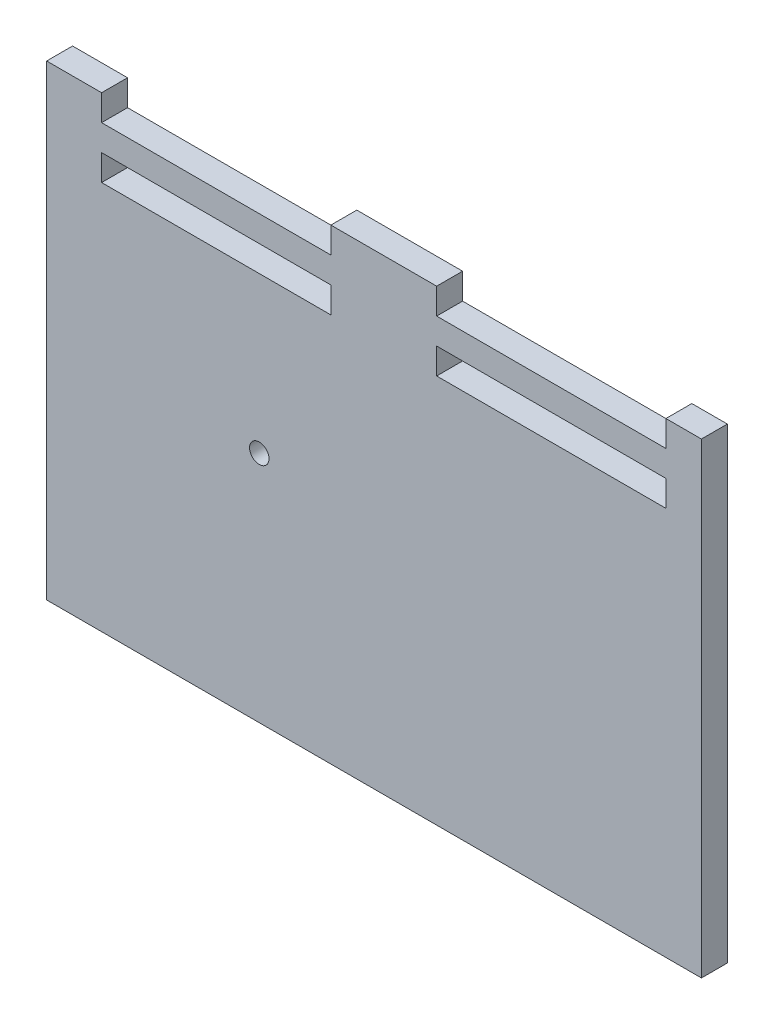
SolidWorks part; units mm, degrees
ref_plane "Front Plane" through (0, 0, 0) normal (0, 0, 1) x (1, 0, 0)
ref_plane "Top Plane" through (0, 0, 0) normal (0, 1, 0) x (1, 0, 0)
ref_plane "Right Plane" through (0, 0, 0) normal (1, 0, 0) x (0, 0, -1)
sketch "Sketch1" plane through (0, 0, 0) normal (0, 0, 1) x (1, 0, 0)
  line L1 (0, 0) -> (304.8, 0)
  line L2 (0, 0) -> (0, 228.6)
  line L3 (0, 228.6) -> (304.8, 228.6)
  line L4 (304.8, 0) -> (304.8, 228.6)
  dimension "D1" = 304.8
  dimension "D2" = 228.6
extrude "Boss-Extrude1" add sketch "Sketch1" along normal blind 12.7
sketch "Sketch2" plane through (0, 0, 12.7) normal (0, 0, 1) x (1, 0, 0)
  line L0 (304.8, 228.6) -> (0, 228.6) construction
  line L1 (0, 228.6) -> (0, 0) construction
  circle A0 centre (91.44, 114.3) radius 4.7625
  dimension "D1" = 9.525
  dimension "D2" = 114.3
  dimension "D3" = 91.44
extrude "Cut-Extrude1" cut sketch "Sketch2" against normal blind 12.7
sketch "Sketch6" plane through (0, 0, 12.7) normal (0, 0, 1) x (1, 0, 0)
  line L0 (0, 114.3) -> (304.8, 114.3) construction
  line L1 (0, 228.6) -> (0, 0) construction
  line L2 (304.8, 0) -> (304.8, 228.6) construction
sketch "Sketch7" plane through (0, 0, 12.7) normal (0, 0, 1) x (1, 0, 0)
  line L1 (14.224, 228.6) -> (126.492, 228.6)
  line L2 (14.224, 228.6) -> (14.224, 215.9)
  line L3 (14.224, 215.9) -> (126.492, 215.9)
  line L4 (0, 228.6) -> (0, 0)
  line L5 (0, 0) -> (304.8, 0)
  line L6 (304.8, 0) -> (304.8, 228.6)
  line L7 (304.8, 228.6) -> (0, 228.6)
  line L8 (0, 228.6) -> (0, 0)
  line L9 (0, 0) -> (304.8, 0)
  line L10 (304.8, 0) -> (304.8, 228.6)
  line L11 (304.8, 228.6) -> (0, 228.6)
  line L12 (126.492, 228.6) -> (126.492, 215.9)
  line L13 (178.308, 228.6) -> (290.576, 228.6)
  line L14 (178.308, 228.6) -> (178.308, 215.9)
  line L15 (178.308, 215.9) -> (290.576, 215.9)
  line L16 (290.576, 228.6) -> (290.576, 215.9)
  line L17 (14.224, 203.2) -> (126.492, 203.2)
  line L18 (14.224, 203.2) -> (14.224, 190.5)
  line L19 (14.224, 190.5) -> (126.492, 190.5)
  line L20 (126.492, 203.2) -> (126.492, 190.5)
  line L21 (178.308, 203.2) -> (290.576, 203.2)
  line L22 (178.308, 203.2) -> (178.308, 190.5)
  line L23 (178.308, 190.5) -> (290.576, 190.5)
  line L24 (290.576, 203.2) -> (290.576, 190.5)
  point P20 (70.358, 203.2)
  line M17 (304.8, 228.6) -> (0, 228.6)
  dimension "D2" = 14.224
  dimension "D3" = 112.268
  dimension "D4" = 112.268
  dimension "D5" = 14.224
  dimension "D6" = 12.7
  dimension "D7" = 12.7
  dimension "D8" = 12.7
  dimension "D9" = 112.268
  dimension "D10" = 112.268
  dimension "D11" = 12.7
  dimension "D12" = 12.7
  dimension "D1" = 0
extrude "Cut-Extrude2" cut sketch "Sketch7" against normal blind 12.7 contours L12 L2 L3 M17 | L15 L16 L13 L14 | L18 L17 L20 L19 | L22 L21 L24 L23 region at (70.358, 222.25, 12.7)
sketch "Sketch8" plane through (0, 0, 12.7) normal (0, 0, 1) x (1, 0, 0)
  line L1 (304.8, 228.6) -> (307.975, 228.6)
  line L2 (304.8, 228.6) -> (304.8, 0)
  line L3 (304.8, 0) -> (307.975, 0)
  line L4 (307.975, 228.6) -> (307.975, 0)
  line L5 (0, 228.6) -> (-12.7, 228.6)
  line L6 (0, 228.6) -> (0, 0)
  line L7 (0, 0) -> (-12.7, 0)
  line L8 (-12.7, 228.6) -> (-12.7, 0)
  line L12 (290.576, 215.9) -> (178.308, 215.9)
  line L13 (178.308, 215.9) -> (178.308, 228.6)
  line L14 (178.308, 228.6) -> (126.492, 228.6)
  line L15 (126.492, 228.6) -> (126.492, 215.9)
  line L16 (126.492, 215.9) -> (14.224, 215.9)
  line L17 (14.224, 215.9) -> (14.224, 228.6)
  line L18 (14.224, 228.6) -> (0, 228.6)
  line L19 (0, 228.6) -> (0, 0)
  line L20 (0, 0) -> (304.8, 0)
  line L21 (304.8, 0) -> (304.8, 228.6)
  line L22 (304.8, 228.6) -> (290.576, 228.6)
  line L23 (290.576, 228.6) -> (290.576, 215.9)
  line L24 (290.576, 215.9) -> (178.308, 215.9)
  line L25 (178.308, 215.9) -> (178.308, 228.6)
  line L26 (178.308, 228.6) -> (126.492, 228.6)
  line L27 (126.492, 228.6) -> (126.492, 215.9)
  line L28 (126.492, 215.9) -> (14.224, 215.9)
  line L29 (14.224, 215.9) -> (14.224, 228.6)
  line L30 (14.224, 228.6) -> (0, 228.6)
  line L31 (0, 228.6) -> (0, 0)
  line L32 (0, 0) -> (304.8, 0)
  line L33 (304.8, 0) -> (304.8, 228.6)
  line L34 (304.8, 228.6) -> (290.576, 228.6)
  line L35 (290.576, 228.6) -> (290.576, 215.9)
  line M22 (0, 228.6) -> (0, 0)
  line M24 (304.8, 0) -> (304.8, 228.6)
  dimension "D2" = 12.7
  dimension "D3" = 3.175
  dimension "D1" = 0
extrude "Boss-Extrude2" add sketch "Sketch8" against normal blind 12.7 contours L5 L8 L7 M22 | L4 L1 L3 M24 region at (306.3875, 114.3, 12.7) region at (-6.35, 114.3, 12.7)
